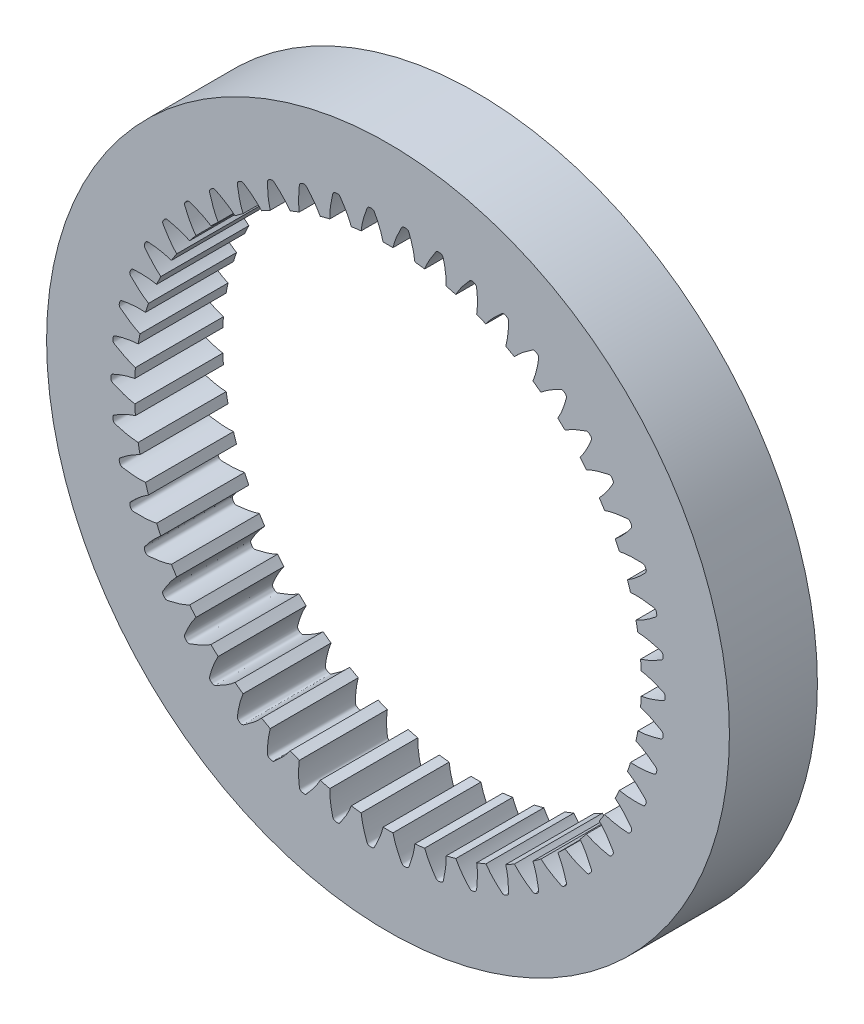
SolidWorks part; units mm, degrees
material "Д16 ГОСТ 4784-97"
ref_plane "FRONT" through (0, 0, 0) normal (0, 0, 1) x (1, 0, 0)
ref_plane "TOP" through (0, 0, 0) normal (0, 1, 0) x (1, 0, 0)
ref_plane "RIGHT" through (0, 0, 0) normal (1, 0, 0) x (0, 0, -1)
ref_axis "Ось1" through (0, 0, 50) along (0, 0, -1)
sketch "SketchRevolveSpurGear" plane through (0, 0, 0) normal (1, 0, 0) x (0, 0, -1)
  line L0 (0, 0) -> (1, 0) construction
  line L1 (-5, 28.8) -> (-5, 38.8)
  line L2 (-5, 38.8) -> (5, 38.8)
  line L3 (5, 38.8) -> (5, 28.8)
  line L4 (5, 28.8) -> (-5, 28.8)
  dimension "MinorDiameter" = 28.8
  dimension "D1" = 10
revolve "SpurGear" add sketch "SketchRevolveSpurGear" angle 360 about L0
sketch "SketchToothSpurGear" plane through (0, 0, 0) normal (0, 0, 1) x (1, 0, 0)
  arc A0 (28.7374, -1.2539) -> (28.7374, 1.2539) centre (0, 0) ccw
  spline S0 degree 3 poles (28.7374, 1.2539) (28.864, 1.2339) (29.065, 1.1954) (29.3463, 1.1293) (29.5911, 1.0642) (29.8572, 0.9849) (30.144, 0.8904) (30.4505, 0.7786) (30.7777, 0.6514) (31.0718, 0.5156) (31.2854, 0.4361) (31.3794, 0.3655) (31.4151, 0.3289) (31.4453, 0.2878) (31.4694, 0.2427) (31.4928, 0.1796) (31.5009, 0.1131) (31.4998, 0.048) (31.5001, 0) (31.4998, -0.048) (31.5009, -0.1131) (31.4928, -0.1796) (31.4694, -0.2427) (31.4453, -0.2878) (31.4151, -0.3289) (31.3794, -0.3655) (31.2854, -0.4361) (31.0718, -0.5156) (30.7777, -0.6514) (30.4505, -0.7786) (30.144, -0.8904) (29.8572, -0.9849) (29.5911, -1.0642) (29.3463, -1.1293) (29.065, -1.1954) (28.864, -1.2339) (28.7374, -1.2539) knots 0 0 0 0 0.060157 0.095945 0.135541 0.178944 0.226153 0.277169 0.331993 0.390623 0.429646 0.437605 0.445564 0.453522 0.461481 0.46944 0.484978 0.492489 0.5 0.507511 0.515022 0.53056 0.538519 0.546478 0.554436 0.562395 0.570354 0.609377 0.668007 0.722831 0.773847 0.821056 0.864459 0.904055 0.939843 1 1 1 1
extrude "ToothExtrudeCutSpurGear" cut sketch "SketchToothSpurGear" against normal blind 5 and the other way blind 5
pattern_circular "PatternSpurGear" count 50 every 7.2 about axis through (0, 0, 50) along (0, 0, -1) of "ToothExtrudeCutSpurGear"
sketch "AuxiliarySketchSpurGear" plane through (0, 0, 0) normal (0, 0, 1) x (1, 0, 0)
  circle A0 centre (0, 0) radius 30 construction
  circle A1 centre (0, 0) radius 28.1908 construction
  circle A2 centre (0, 0) radius 31.5 construction
  circle A3 centre (0, 0) radius 28.8 construction
  dimension "PitchDiameter" = 60
  dimension "BaseDiameter" = 56.3816
  dimension "MajorDiameter" = 63
  dimension "MinorDiameter" = 57.6
